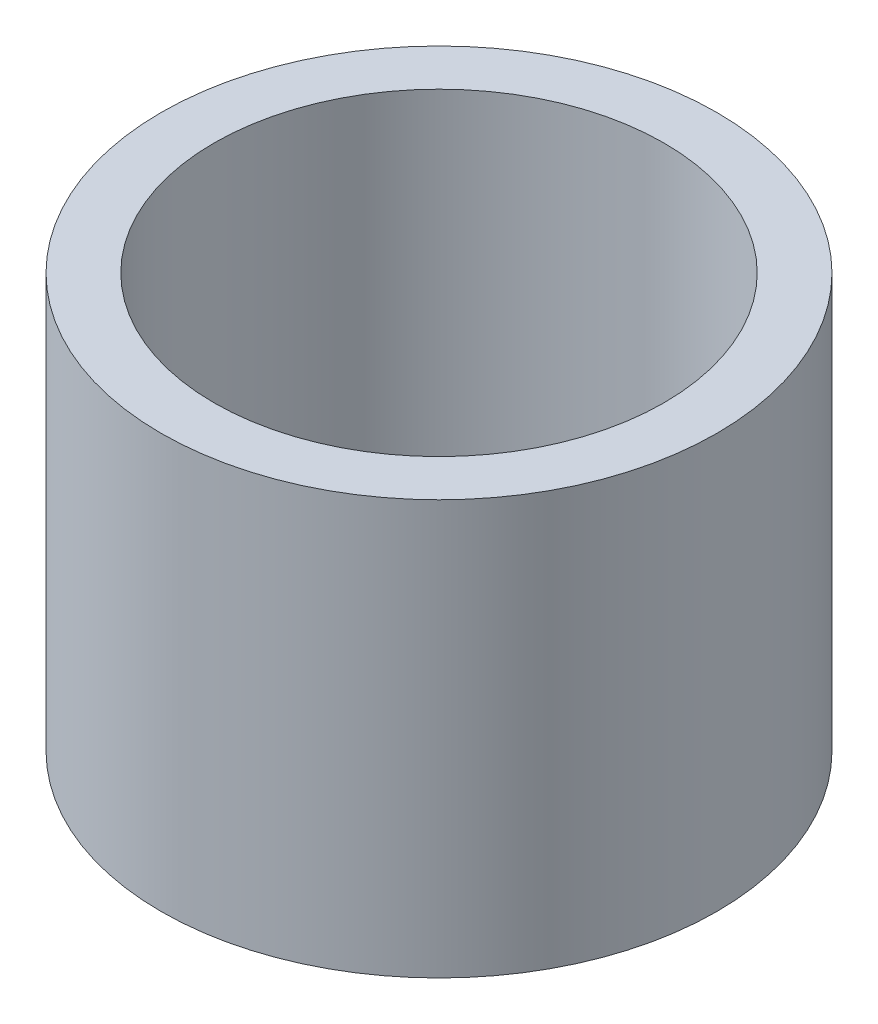
SolidWorks part; units mm, degrees
material "Copper"
ref_plane "Front Plane" through (0, 0, 0) normal (0, 0, 1) x (1, 0, 0)
ref_plane "Top Plane" through (0, 0, 0) normal (0, 1, 0) x (1, 0, 0)
ref_plane "Right Plane" through (0, 0, 0) normal (1, 0, 0) x (0, 0, -1)
ref_axis "Axial" through (0, 3.81, 0) along (0, -1, 0)
ref_plane "Bottom Plane" through (0, -76.2, 0) normal (0, 1, 0) x (1, 0, 0)
sketch "Sketch1" plane through (0, 0, 0) normal (0, 1, 0) x (1, 0, 0)
  circle A0 centre (0, 0) radius 41.402
  circle A1 centre (0, 0) radius 51.1302
  dimension "D1" = 102.2604
  dimension "D2" = 82.804
extrude "Ablative" add sketch "Sketch1" against normal blind 76.2
